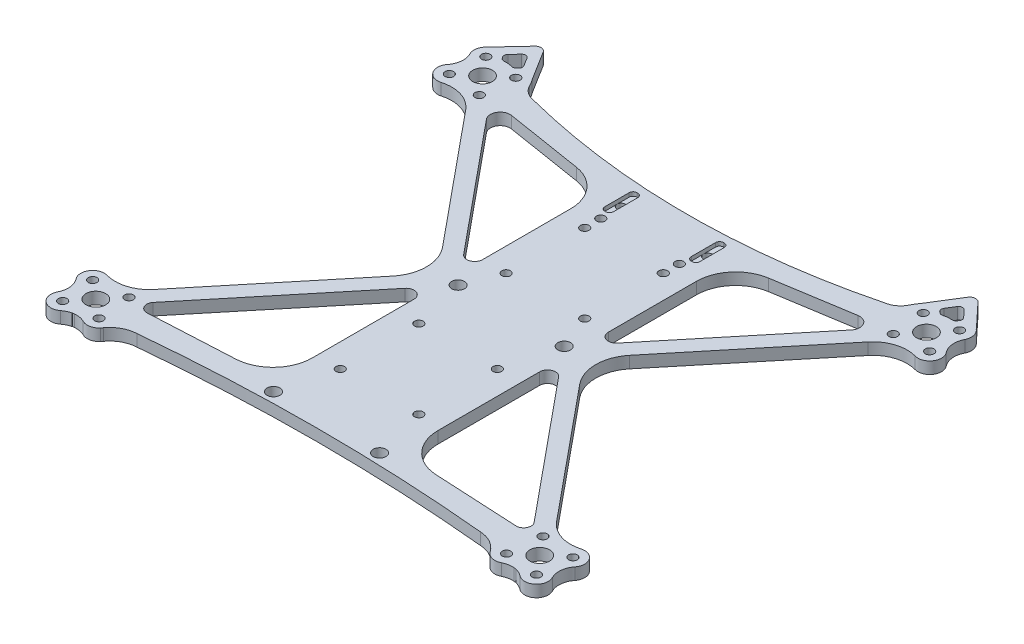
SolidWorks part; units mm, degrees
ref_plane "Front Plane" through (0, 0, 0) normal (0, 0, 1) x (1, 0, 0)
ref_plane "Top Plane" through (0, 0, 0) normal (0, 1, 0) x (1, 0, 0)
ref_plane "Right Plane" through (0, 0, 0) normal (1, 0, 0) x (0, 0, -1)
sketch "Sketch1" plane through (0, 0, 0) normal (0, 1, 0) x (1, 0, 0)
  line L0 (0, 42.225) -> (0, -42.225) construction
  line L1 (16, 42.225) -> (-16, 42.225)
  line L2 (16, 42.225) -> (16, -42.225)
  line L3 (16, -42.225) -> (-16, -42.225)
  line L4 (-16, 42.225) -> (-16, -42.225)
  line L5 (16, 42.225) -> (-16, -42.225) construction
  line L6 (16, -42.225) -> (-16, 42.225) construction
  line L17 (-16, 42.225) -> (16, 42.225)
  line L19 (-16, 42.225) -> (-16, 52.425)
  line L20 (-10, 36) -> (10, 36)
  line L21 (-10, 36) -> (-10, 16)
  line L22 (-10, 16) -> (10, 16)
  line L23 (10, 36) -> (10, 16)
  line L24 (-10, 36) -> (10, 16) construction
  line L25 (-10, 16) -> (10, 36) construction
  line L26 (-14.5, 10.775) -> (14.5, 10.775)
  line L27 (-14.5, 10.775) -> (-14.5, 41.225)
  line L28 (-14.5, 41.225) -> (14.5, 41.225)
  line L29 (14.5, 10.775) -> (14.5, 41.225)
  line L30 (-14.5, 10.775) -> (14.5, 41.225) construction
  line L31 (-14.5, 41.225) -> (14.5, 10.775) construction
  line L32 (-10, -6.225) -> (10, -6.225)
  line L33 (-10, -6.225) -> (-10, -26.225)
  line L34 (-10, -26.225) -> (10, -26.225)
  line L35 (10, -6.225) -> (10, -26.225)
  line L36 (-10, -6.225) -> (10, -26.225) construction
  line L37 (-10, -26.225) -> (10, -6.225) construction
  line L38 (-15.75, -36.225) -> (15.75, -36.225)
  line L39 (-15.75, -36.225) -> (-15.75, 3.775)
  line L40 (-15.75, 3.775) -> (15.75, 3.775)
  line L41 (15.75, -36.225) -> (15.75, 3.775)
  line L42 (-15.75, -36.225) -> (15.75, 3.775) construction
  line L43 (-15.75, 3.775) -> (15.75, -36.225) construction
  line L58 (-16, 52.425) -> (16, 52.425)
  line L63 (-12.1, 50.425) -> (-9.9, 50.425)
  line L64 (-12.1, 50.425) -> (-12.1, 42.225)
  line L65 (-12.1, 42.225) -> (-9.9, 42.225)
  line L66 (-9.9, 50.425) -> (-9.9, 42.225)
  line L67 (-12.1, 50.425) -> (-9.9, 42.225) construction
  line L68 (-12.1, 42.225) -> (-9.9, 50.425) construction
  line L78 (12.1, 50.425) -> (9.9, 50.425)
  line L79 (12.1, 50.425) -> (12.1, 42.225)
  line L80 (12.1, 42.225) -> (9.9, 42.225)
  line L81 (9.9, 50.425) -> (9.9, 42.225)
  line L82 (-14.5, 10.775) -> (-14.5, 3.775) construction
  line L83 (-14.5, 7.275) -> (16, 7.275) construction
  line L89 (-13.5, -37.225) -> (-16, -37.225) construction
  line L90 (16, 42.225) -> (16, 52.425)
  circle A3 centre (-10, 36) radius 1.1
  circle A4 centre (10, 36) radius 1.1
  circle A5 centre (10, 16) radius 1.1
  circle A6 centre (-10, 16) radius 1.1
  circle A7 centre (-10, -6.225) radius 1.1
  circle A8 centre (10, -6.225) radius 1.1
  circle A9 centre (10, -26.225) radius 1.1
  circle A10 centre (-10, -26.225) radius 1.1
  circle A37 centre (-13.5, 7.275) radius 2.5
  circle A38 centre (-13.5, 7.275) radius 1.625
  circle A39 centre (13.5, 7.275) radius 1.625
  circle A40 centre (-13.5, -39.725) radius 2.5
  circle A41 centre (-13.5, -39.725) radius 1.625
  circle A42 centre (13.5, -39.725) radius 1.625
  circle A43 centre (-11, 46.325) radius 1.1
  circle A44 centre (11, 46.325) radius 1.1
  point P0 (0, 0)
  point P8 (0, 0)
  point P16 (0, 26)
  point P26 (0, 26)
  point P31 (0, -16.225)
  point P36 (0, -16.225)
  point P61 (-11, 46.325)
  dimension "D3" = 22
  dimension "D4" = 2
  dimension "D17" = 2.2
  dimension "D22" = 5
  dimension "D23" = 3.25
  dimension "D8" = 32
  dimension "D10" = 20
  dimension "D11" = 29
  dimension "D12" = 30.45
  dimension "D13" = 40
  dimension "D14" = 31.5
  dimension "D15" = 1
  dimension "D16" = 7
  dimension "D18" = 2.2
  dimension "D20" = 8.2
  dimension "D24" = 1
extrude "Base shape" add sketch "Sketch1" along normal blind 2 contours L1 L90 L58 L19 L17 L64 L63 L66 L81 L78 L79 | A43 L64 L17 L66 | A43 L66 L63 L64 | L81 A44 L79 L78 | L79 A44 L81 L17 | L4 L3 L2 L1 | A3 | A4 | A6 | A5 | A39 | A38 | A7 | A8 | A9 | A10 | A41 | A42 region at (0, 0, -47.4493) region at (11, 0, -43.8523) region at (11, 0, -48.7977) region at (-11, 0, -43.8523) region at (-11, 0, -48.7977)
sketch "Sketch2" plane through (0, 2, 0) normal (0, -1, 0) x (1, 0, 0)
  line L0 (0, -52.425) -> (0, 42.225) construction
  line L1 (11.1, -42.225) -> (10.9, -42.225)
  line L2 (12.1, -43.225) -> (12.1, -49.425)
  line L3 (11.1, -50.425) -> (10.9, -50.425)
  line L4 (9.9, -43.225) -> (9.9, -49.425)
  line L5 (12.1, -42.225) -> (9.9, -50.425) construction
  line L6 (12.1, -50.425) -> (9.9, -42.225) construction
  line L12 (16, 42.225) -> (-16, 42.225) construction
  line L13 (-11.1, -42.225) -> (-10.9, -42.225)
  line L14 (-12.1, -43.225) -> (-12.1, -49.425)
  line L15 (-11.1, -50.425) -> (-10.9, -50.425)
  line L20 (-9.9, -43.225) -> (-9.9, -49.425)
  line L21 (-16, -52.425) -> (16, -52.425) construction
  arc A2 (12.1, -49.425) -> (11.1, -50.425) centre (11.1, -49.425) cw
  arc A3 (10.9, -50.425) -> (9.9, -49.425) centre (10.9, -49.425) cw
  arc A4 (10.9, -42.225) -> (9.9, -43.225) centre (10.9, -43.225) ccw
  arc A5 (11.1, -42.225) -> (12.1, -43.225) centre (11.1, -43.225) cw
  arc A6 (-10.9, -42.225) -> (-9.9, -43.225) centre (-10.9, -43.225) cw
  arc A7 (-11.1, -42.225) -> (-12.1, -43.225) centre (-11.1, -43.225) ccw
  arc A8 (-12.1, -49.425) -> (-11.1, -50.425) centre (-11.1, -49.425) ccw
  arc A9 (-10.9, -50.425) -> (-9.9, -49.425) centre (-10.9, -49.425) ccw
  point P0 (11, -46.325)
  dimension "D3" = 1
  dimension "D1" = 8.2
  dimension "D2" = 2.2
extrude "Cut-Extrude2" cut sketch "Sketch2" along normal blind 1
sketch "Sketch3" plane through (0, 2, 0) normal (0, 1, 0) x (1, 0, 0)
  line L0 (-11.1, 50.425) -> (-10.9, 50.425) construction
  line L1 (-9.9, 49.425) -> (-9.9, 43.225) construction
  line L2 (-10.9, 42.225) -> (-11.1, 42.225) construction
  line L3 (-12.1, 43.225) -> (-12.1, 49.425) construction
  line L4 (-11.1, 50.425) -> (-10.9, 50.425)
  line L5 (-9.9, 49.425) -> (-9.9, 43.225)
  line L6 (-10.9, 42.225) -> (-11.1, 42.225)
  line L7 (-12.1, 43.225) -> (-12.1, 49.425)
  line L8 (-16, 52.425) -> (-16, -42.225)
  line L9 (-16, 52.425) -> (-16, -42.225)
  line L10 (-16, -42.225) -> (16, -42.225)
  line L11 (16, -42.225) -> (16, 52.425)
  line L12 (10.9, 50.425) -> (11.1, 50.425) construction
  line L13 (12.1, 49.425) -> (12.1, 43.225) construction
  line L14 (11.1, 42.225) -> (10.9, 42.225) construction
  line L15 (9.9, 43.225) -> (9.9, 49.425) construction
  line L18 (-16, -42.225) -> (16, -42.225)
  line L24 (10.9, 50.425) -> (11.1, 50.425)
  line L25 (12.1, 49.425) -> (12.1, 43.225)
  line L30 (11.1, 42.225) -> (10.9, 42.225)
  line L31 (9.9, 43.225) -> (9.9, 49.425)
  line L36 (16, -42.225) -> (16, 52.425)
  line L37 (16, 52.425) -> (-16, 52.425)
  line L38 (16, 52.425) -> (-16, 52.425)
  circle A0 centre (13.5, -39.725) radius 1.625 construction
  circle A1 centre (-13.5, -39.725) radius 1.625 construction
  circle A2 centre (-13.5, 7.275) radius 1.625 construction
  circle A3 centre (-10, -6.225) radius 1.1 construction
  circle A4 centre (-10, -26.225) radius 1.1 construction
  circle A5 centre (10, -26.225) radius 1.1 construction
  circle A6 centre (10, -6.225) radius 1.1 construction
  circle A7 centre (13.5, 7.275) radius 1.625 construction
  arc A13 (-11.1, 50.425) -> (-12.1, 49.425) centre (-11.1, 49.425) ccw construction
  arc A14 (-9.9, 49.425) -> (-10.9, 50.425) centre (-10.9, 49.425) ccw construction
  circle A24 centre (-10, 16) radius 1.1 construction
  circle A25 centre (-10, 36) radius 1.1 construction
  circle A26 centre (10, 36) radius 1.1 construction
  circle A27 centre (10, 16) radius 1.1 construction
  circle A28 centre (10, 16) radius 1.1
  circle A29 centre (10, 36) radius 1.1
  circle A30 centre (-10, 36) radius 1.1
  circle A31 centre (-10, 16) radius 1.1
  circle A32 centre (13.5, 7.275) radius 1.625
  circle A33 centre (10, -6.225) radius 1.1
  circle A34 centre (10, -26.225) radius 1.1
  circle A35 centre (-10, -26.225) radius 1.1
  circle A36 centre (-10, -6.225) radius 1.1
  circle A37 centre (13.5, -39.725) radius 1.625
  circle A38 centre (-13.5, -39.725) radius 1.625
  circle A39 centre (-13.5, 7.275) radius 1.625
  arc A40 (-10.9, 42.225) -> (-9.9, 43.225) centre (-10.9, 43.225) ccw construction
  arc A41 (-12.1, 43.225) -> (-11.1, 42.225) centre (-11.1, 43.225) ccw construction
  arc A42 (-11.1, 50.425) -> (-12.1, 49.425) centre (-11.1, 49.425) ccw
  arc A43 (-9.9, 49.425) -> (-10.9, 50.425) centre (-10.9, 49.425) ccw
  arc A44 (-10.9, 42.225) -> (-9.9, 43.225) centre (-10.9, 43.225) ccw
  arc A45 (-12.1, 43.225) -> (-11.1, 42.225) centre (-11.1, 43.225) ccw
  arc A46 (10.9, 50.425) -> (9.9, 49.425) centre (10.9, 49.425) ccw construction
  arc A47 (12.1, 49.425) -> (11.1, 50.425) centre (11.1, 49.425) ccw construction
  arc A48 (11.1, 42.225) -> (12.1, 43.225) centre (11.1, 43.225) ccw construction
  arc A49 (9.9, 43.225) -> (10.9, 42.225) centre (10.9, 43.225) ccw construction
  arc A50 (10.9, 50.425) -> (9.9, 49.425) centre (10.9, 49.425) ccw
  arc A51 (12.1, 49.425) -> (11.1, 50.425) centre (11.1, 49.425) ccw
  arc A52 (11.1, 42.225) -> (12.1, 43.225) centre (11.1, 43.225) ccw
  arc A53 (9.9, 43.225) -> (10.9, 42.225) centre (10.9, 43.225) ccw
  dimension "D1" = 0
extrude "Thicker base" add sketch "Sketch3" along normal blind 1
sketch "Sketch8" plane through (0, 1, 0) normal (0, 1, 0) x (1, 0, 0)
  line L0 (9.9, 46.325) -> (9.9, 43.225) construction
  line L1 (10.9, 42.225) -> (11.1, 42.225) construction
  line L2 (12.1, 43.225) -> (12.1, 46.325) construction
  line L3 (12.1, 46.325) -> (12.1, 49.425) construction
  line L4 (11.1, 50.425) -> (10.9, 50.425) construction
  line L5 (9.9, 49.425) -> (9.9, 46.325) construction
  line L6 (-12.1, 46.325) -> (-12.1, 43.225) construction
  line L7 (-11.1, 42.225) -> (-10.9, 42.225) construction
  line L8 (-9.9, 43.225) -> (-9.9, 46.325) construction
  line L9 (-9.9, 46.325) -> (-9.9, 49.425) construction
  line L10 (-10.9, 50.425) -> (-11.1, 50.425) construction
  line L11 (-12.1, 49.425) -> (-12.1, 46.325) construction
  line L12 (9.9, 46.325) -> (9.9, 43.225)
  line L13 (10.9, 42.225) -> (11.1, 42.225)
  line L14 (12.1, 43.225) -> (12.1, 46.325)
  line L15 (12.1, 46.325) -> (12.1, 49.425)
  line L16 (11.1, 50.425) -> (10.9, 50.425)
  line L17 (9.9, 49.425) -> (9.9, 46.325)
  line L18 (-12.1, 46.325) -> (-12.1, 43.225)
  line L19 (-11.1, 42.225) -> (-10.9, 42.225)
  line L20 (-9.9, 43.225) -> (-9.9, 46.325)
  line L21 (-9.9, 46.325) -> (-9.9, 49.425)
  line L22 (-10.9, 50.425) -> (-11.1, 50.425)
  line L23 (-12.1, 49.425) -> (-12.1, 46.325)
  arc A0 (9.9, 46.325) -> (12.1, 46.325) centre (11, 46.325) ccw construction
  arc A1 (9.9, 43.225) -> (10.9, 42.225) centre (10.9, 43.225) ccw construction
  arc A2 (11.1, 42.225) -> (12.1, 43.225) centre (11.1, 43.225) ccw construction
  arc A3 (12.1, 46.325) -> (9.9, 46.325) centre (11, 46.325) ccw construction
  arc A4 (12.1, 49.425) -> (11.1, 50.425) centre (11.1, 49.425) ccw construction
  arc A5 (10.9, 50.425) -> (9.9, 49.425) centre (10.9, 49.425) ccw construction
  arc A6 (-12.1, 43.225) -> (-11.1, 42.225) centre (-11.1, 43.225) ccw construction
  arc A7 (-10.9, 42.225) -> (-9.9, 43.225) centre (-10.9, 43.225) ccw construction
  arc A8 (-12.1, 46.325) -> (-9.9, 46.325) centre (-11, 46.325) ccw construction
  arc A9 (-9.9, 49.425) -> (-10.9, 50.425) centre (-10.9, 49.425) ccw construction
  arc A10 (-11.1, 50.425) -> (-12.1, 49.425) centre (-11.1, 49.425) ccw construction
  arc A11 (-9.9, 46.325) -> (-12.1, 46.325) centre (-11, 46.325) ccw construction
  arc A12 (9.9, 46.325) -> (12.1, 46.325) centre (11, 46.325) ccw
  arc A13 (9.9, 43.225) -> (10.9, 42.225) centre (10.9, 43.225) ccw
  arc A14 (11.1, 42.225) -> (12.1, 43.225) centre (11.1, 43.225) ccw
  arc A15 (12.1, 46.325) -> (9.9, 46.325) centre (11, 46.325) ccw
  arc A16 (12.1, 49.425) -> (11.1, 50.425) centre (11.1, 49.425) ccw
  arc A17 (10.9, 50.425) -> (9.9, 49.425) centre (10.9, 49.425) ccw
  arc A18 (-12.1, 43.225) -> (-11.1, 42.225) centre (-11.1, 43.225) ccw
  arc A19 (-10.9, 42.225) -> (-9.9, 43.225) centre (-10.9, 43.225) ccw
  arc A20 (-12.1, 46.325) -> (-9.9, 46.325) centre (-11, 46.325) ccw
  arc A21 (-9.9, 49.425) -> (-10.9, 50.425) centre (-10.9, 49.425) ccw
  arc A22 (-11.1, 50.425) -> (-12.1, 49.425) centre (-11.1, 49.425) ccw
  arc A23 (-9.9, 46.325) -> (-12.1, 46.325) centre (-11, 46.325) ccw
  line M1 (-9.9, 46.325) -> (-9.9, 49.425)
  arc M2 (-9.9, 49.425) -> (-10.9, 50.425) centre (-10.9, 49.425) ccw
  line M3 (-10.9, 50.425) -> (-11.1, 50.425)
  arc M4 (-11.1, 50.425) -> (-12.1, 49.425) centre (-11.1, 49.425) ccw
  line M5 (-12.1, 49.425) -> (-12.1, 46.325)
  arc M6 (-12.1, 46.325) -> (-9.9, 46.325) centre (-11, 46.325) cw
extrude "Thicker camera mount pocket" add sketch "Sketch8" along normal offset from surface (1 mm away) 1 contours A20 L18 A18 L19 A19 L20 | M6 M1 M2 M3 M4 M5 | L16 A17 L17 A15 L15 A16 | L13 A14 L14 A12 L12 A13 region at (11, 1, -43.9424) region at (11, 1, -48.7076) region at (-11, 1, -43.9424) region at (-11, 1, -48.7076) up to face at (-13.5, 3, 41.35)
sketch "Sketch4" plane through (0, 0, 0) normal (0, -1, 0) x (1, 0, 0)
  line L0 (0, 13.9568) -> (0, -8.6953) construction
  line L1 (-13.1, -38.5) -> (-6.9, -38.5)
  line L2 (-14.1, -39.5) -> (-14.1, -40.7)
  line L3 (-13.1, -41.7) -> (-6.9, -41.7)
  line L4 (-5.9, -39.5) -> (-5.9, -40.7)
  line L5 (-10, -38.5) -> (-10, -41.7) construction
  line L7 (13.1, -38.5) -> (6.9, -38.5)
  line L8 (14.1, -39.5) -> (14.1, -40.7)
  line L9 (13.1, -41.7) -> (6.9, -41.7)
  line L10 (5.9, -39.5) -> (5.9, -40.7)
  line L12 (-14.1, -40.1) -> (-5.9, -40.1) construction
  circle A0 centre (-10, -36) radius 2
  arc A9 (14.1, -40.7) -> (13.1, -41.7) centre (13.1, -40.7) cw
  arc A10 (13.1, -38.5) -> (14.1, -39.5) centre (13.1, -39.5) cw
  arc A11 (6.9, -41.7) -> (5.9, -40.7) centre (6.9, -40.7) cw
  arc A12 (6.9, -38.5) -> (5.9, -39.5) centre (6.9, -39.5) ccw
  arc A13 (-6.9, -41.7) -> (-5.9, -40.7) centre (-6.9, -40.7) ccw
  arc A14 (-6.9, -38.5) -> (-5.9, -39.5) centre (-6.9, -39.5) cw
  arc A15 (-14.1, -40.7) -> (-13.1, -41.7) centre (-13.1, -40.7) ccw
  arc A16 (-13.1, -38.5) -> (-14.1, -39.5) centre (-13.1, -39.5) ccw
  point P9 (-10, -38)
  point P19 (14.1, -41.7)
  point P24 (14.1, -38.5)
  point P27 (5.9, -41.7)
  point P30 (5.9, -38.5)
  point P33 (-5.9, -41.7)
  point P36 (-5.9, -38.5)
  point P39 (-14.1, -41.7)
  point P42 (-14.1, -38.5)
  dimension "D5" = 4
  dimension "D6" = 1
  dimension "D1" = 8.2
  dimension "D2" = 3.2
  dimension "D3" = 10
  dimension "D4" = 0.5
extrude "Battery holder pockets" cut sketch "Sketch4" against normal blind 1 contours L4 L1 L2 L3 | L7 L10 L9 L8 region at (-10, 0, -40.1) region at (10, 0, -40.1)
sketch "Sketch5" plane through (0, 1, 0) normal (0, -1, 0) x (1, 0, 0)
  line L0 (-10, -38.5) -> (-10, -41.7) construction
  line L2 (-13.1, -41.7) -> (-6.9, -41.7) construction
  line L3 (0, 5.9884) -> (0, -5.6723) construction
  line L4 (-13.1, -38.5) -> (-6.9, -38.5) construction
  circle A0 centre (-10, -40.1) radius 1.1
  circle A1 centre (10, -40.1) radius 1.1
  dimension "D1" = 2.2
extrude "Battery holder holes" cut sketch "Sketch5" against normal up to next
sketch "Sketch6" [suppressed] plane through (0, 0, 0) normal (0, -1, 0) x (1, 0, 0)
  line L0 (0, -5.1) -> (0, 9.653) construction
  line L1 (16, 42.225) -> (16, -52.425) construction
  line L8 (-13.5, -7.275) -> (13.5, -7.275) construction
  line L10 (-16, -25.775) -> (16, -25.775) construction
  line L13 (17.5, -34.275) -> (19, -34.275)
  line L14 (16, -37.275) -> (19, -37.275)
  line L15 (16, -37.275) -> (16, -14.275)
  line L16 (16, -14.275) -> (19, -14.275)
  line L17 (19, -37.275) -> (19, -14.275)
  line L18 (16, -37.275) -> (19, -14.275) construction
  line L19 (16, -14.275) -> (19, -37.275) construction
  line L20 (16, -35.775) -> (17.5, -35.775)
  line L21 (16, -35.775) -> (16, -15.775)
  line L22 (16, -15.775) -> (17.5, -15.775)
  line L23 (17.5, -35.775) -> (17.5, -15.775)
  line L24 (16, -35.775) -> (17.5, -15.775) construction
  line L25 (16, -15.775) -> (17.5, -35.775) construction
  line L26 (17.5, -17.275) -> (19, -17.275)
  line L27 (-17.5, -34.275) -> (-19, -34.275)
  line L28 (-17.5, -17.275) -> (-19, -17.275)
  line L29 (-16, -35.775) -> (-16, -15.775)
  line L30 (-16, -35.775) -> (-17.5, -35.775)
  line L31 (-17.5, -35.775) -> (-17.5, -15.775)
  line L32 (-16, -15.775) -> (-17.5, -15.775)
  line L33 (-16, -37.275) -> (-16, -14.275)
  line L34 (-16, -37.275) -> (-19, -37.275)
  line L35 (-19, -37.275) -> (-19, -14.275)
  line L36 (-16, -14.275) -> (-19, -14.275)
  line L37 (16, 22.725) -> (19, 22.725)
  line L38 (16, 22.725) -> (16, -0.275)
  line L39 (16, -0.275) -> (19, -0.275)
  line L40 (19, 22.725) -> (19, -0.275)
  line L41 (16, 21.225) -> (17.5, 21.225)
  line L42 (16, 21.225) -> (16, 1.225)
  line L43 (16, 1.225) -> (17.5, 1.225)
  line L44 (17.5, 21.225) -> (17.5, 1.225)
  line L45 (17.5, 2.725) -> (19, 2.725)
  line L46 (17.5, 19.725) -> (19, 19.725)
  line L47 (-17.5, 19.725) -> (-19, 19.725)
  line L48 (-17.5, 2.725) -> (-19, 2.725)
  line L49 (-16, 21.225) -> (-16, 1.225)
  line L50 (-16, 21.225) -> (-17.5, 21.225)
  line L51 (-17.5, 21.225) -> (-17.5, 1.225)
  line L52 (-16, 1.225) -> (-17.5, 1.225)
  line L53 (-16, 22.725) -> (-16, -0.275)
  line L54 (-16, 22.725) -> (-19, 22.725)
  line L55 (-19, 22.725) -> (-19, -0.275)
  line L56 (-16, -0.275) -> (-19, -0.275)
  point P19 (17.5, -25.775)
  point P25 (16.75, -25.775)
  dimension "D1" = 14
  dimension "D4" = 23
  dimension "D5" = 3
  dimension "D6" = 1.5
  dimension "D7" = 20
  dimension "D8" = 1.5
extrude "Strap holders" [suppressed] add sketch "Sketch6" against normal up to surface (2 mm away) up to face at (-11, 2, -43.6726)
fillet "Strap holder fillets" [suppressed] radius 0.75
fillet "Edge fillets" [suppressed] radius 2.5
sketch "Sketch7" plane through (0, 3, 0) normal (0, 1, 0) x (1, 0, 0)
  line L0 (-56.5, 56.5) -> (-16, 50.0116) construction
  line L1 (56.5, -56.5) -> (-56.5, -56.5)
  line L2 (56.5, -56.5) -> (56.5, 56.5)
  line L3 (56.5, 56.5) -> (-56.5, 56.5)
  line L4 (-56.5, -56.5) -> (-56.5, 56.5)
  line L5 (56.5, -56.5) -> (-56.5, 56.5) construction
  line L6 (56.5, 56.5) -> (-56.5, -56.5) construction
  line L7 (-16, 46.9733) -> (-48.5961, 52.1955)
  line L8 (-16, 4.1271) -> (-52.4693, 48.4531)
  line L9 (-47.647, 58.1199) -> (-12.1, 52.425)
  line L10 (-56.0254, 59.4622) -> (-15.5254, 52.9738) construction
  line L11 (-13.5, 7.275) -> (13.5, 7.275) construction
  line L12 (-63.45, 50.7819) -> (-49.55, 62.2181) construction
  line L13 (-56.5, 56.5) -> (-16, 7.275) construction
  line L14 (-16, 10.4229) -> (-52.4693, -33.9031)
  line L15 (-49.3804, 50.9945) -> (-16, 10.4229)
  line L16 (-16, 4.1271) -> (-16.003, 4.1308)
  line L17 (-56.5, 56.5) -> (-60.3121, 61.1333) construction
  line L18 (-56.5, 65.5) -> (-56.5, 47.5) construction
  line L19 (-60.3121, 61.1333) -> (-51.8667, 60.3121) construction
  line L20 (-56.0894, 60.7227) -> (-55.3151, 68.6852) construction
  line L21 (-56.4116, 69.7087) -> (-62.3842, 63.31)
  line L22 (-54.0419, 69.4782) -> (-49.414, 62.0488)
  line L23 (-55.4603, 67.1922) -> (-58.7341, 63.6848)
  line L24 (-55.4603, 67.1922) -> (-52.9235, 63.1198)
  line L25 (-36.25, 53.2558) -> (-36.7246, 50.2936) construction
  line L26 (-49.3804, -36.4445) -> (-16, 4.1271)
  line L27 (-56.5, -41.95) -> (-13.5, -39.725) construction
  line L28 (-47.871, -44.5075) -> (-3.7595, -42.225)
  line L29 (-48.1811, -38.5155) -> (-16, -36.8503)
  line L30 (-56.345, -44.946) -> (-14.5762, -42.7847) construction
  line L31 (-56.5, -41.95) -> (-14.7312, -39.7887) construction
  line L32 (-16, -42.225) -> (16, -42.225) construction
  line L33 (-56.655, -38.954) -> (-14.8862, -36.7927) construction
  line L34 (-35, -40.8375) -> (-35.155, -37.8415) construction
  line L35 (-12.1, 49.425) -> (-12.1, 52.425) construction
  line L37 (16, 52.425) -> (-16, 52.425) construction
  line L38 (-16, 52.425) -> (-16, -42.225) construction
  line L39 (-54.9556, 57.7707) -> (-12.9111, 6.6685) construction
  line L40 (-56.5, 56.5) -> (-14.4556, 5.3978) construction
  circle A0 centre (-56.5, 56.5) radius 38.1
  circle A1 centre (-56.5, 56.5) radius 9
  circle A2 centre (-56.5, 56.5) radius 6
  circle A3 centre (-51.8667, 60.3121) radius 1.1
  circle A4 centre (-61.1333, 52.6879) radius 1.1
  circle A5 centre (-60.3121, 61.1333) radius 1.1
  circle A6 centre (-52.6879, 51.8667) radius 1.1
  circle A7 centre (-60.3121, 61.1333) radius 3
  circle A8 centre (-51.8667, 60.3121) radius 3
  circle A9 centre (-61.1333, 52.6879) radius 3
  circle A10 centre (-52.6879, 51.8667) radius 3
  circle A12 centre (-56.5, 56.5) radius 2.5
  circle A13 centre (-55.3151, 68.6852) radius 1.5
  circle A14 centre (-67.313, 57.5515) radius 4.864
  circle A16 centre (-43.9819, 62.4587) radius 4.864
  circle A18 centre (-44.5093, 49.0089) radius 2.5
  circle A20 centre (-56.5, -41.95) radius 6
  circle A21 centre (-52.6879, -37.3167) radius 1.1
  circle A22 centre (-61.1333, -38.1379) radius 1.1
  circle A23 centre (-60.3121, -46.5833) radius 1.1
  circle A24 centre (-51.8667, -45.7621) radius 1.1
  circle A25 centre (-51.8667, -45.7621) radius 3
  circle A26 centre (-52.6879, -37.3167) radius 3
  circle A27 centre (-56.5, -41.95) radius 2.5
  circle A28 centre (-60.3121, -46.5833) radius 3
  circle A29 centre (-67.313, -43.0015) radius 4.864
  circle A30 centre (-61.1333, -38.1379) radius 3
  circle A34 centre (-56.5, -41.95) radius 9
  circle A35 centre (-55.4485, -52.763) radius 4.864
  circle A36 centre (-57.9703, 41.3803) radius 8.7417
  circle A37 centre (-57.9703, -26.8303) radius 8.7417
  circle A38 centre (-43.36, -51.5674) radius 7.2836
  circle A39 centre (-47.0369, -36.5665) radius 1.8873
  point P0 (0, 0)
  point P36 (-52.6879, 51.8667)
  point P54 (-55.4603, 67.1922)
  line M26 (-16, -42.225) -> (16, -42.225)
  line M134 (16, 52.425) -> (-16, 52.425)
  line M135 (-16, 52.425) -> (-16, -42.225)
  dimension "D3" = 76.2
  dimension "D4" = 12
  dimension "D5" = 3
  dimension "D10" = 2.2
  dimension "D11" = 5
  dimension "D12" = 3
  dimension "D16" = 5
  dimension "D1" = 113
  dimension "D13" = 8
  dimension "D7" = 3
  dimension "D9" = 2
extrude "Arms" add sketch "Sketch7" against normal up to surface (3 mm away) contours A0 L7 L9 M135 M134 | A1 L7 A0 L9 L3 | A1 L3 L9 | A8 A2 L3 A1 | A16 A1 L9 | A10 A1 L3 A2 | A18 L7 A1 L15 | A2 A8 A3 | A2 A8 A3 | A8 A1 L24 | A13 L24 A1 L22 | A13 | A13 L21 A1 L23 | A7 L23 A1 | A2 A7 A5 | A2 A7 A5 | A12 L3 A2 A8 A7 A9 L4 | A12 L4 A2 A10 L3 | A2 A10 A6 | A10 A2 A6 | A36 A1 A10 | A36 L8 A1 | A36 A10 A2 L4 | A36 L4 A2 A9 | A2 A9 A4 | A2 A9 A4 | A14 A9 A2 | A14 A2 A7 | A1 L8 A0 L15 | A0 L8 L14 L15 | L14 L8 M135 | L14 A34 L26 L8 | L29 A34 L28 M26 M135 | A39 A34 L29 | A39 L26 A34 | L14 A37 A34 | A34 A37 A26 | A34 A26 A20 A25 | A26 A20 A21 | A26 A37 L4 A20 | A26 A20 A21 | L4 A27 A20 A25 A26 | A25 A20 A24 | A38 L28 A34 | A25 A20 A24 | A20 A30 A28 L4 A27 | L4 A37 A30 A20 | A30 A20 A22 | A30 A20 A22 | A20 A30 A29 | A20 A29 A28 | A28 A20 A23 | A28 A20 A23 | A35 L4 A20 A28 | A35 A25 A20 region at (-47.184, 3, 45.066) region at (-31.4436, 3, 40.7044) region at (-32.8289, 3, -52.5874) region at (-44.211, 3, -57.0386) region at (-17.2942, 3, -50.2467) region at (-49.0289, 3, 41.2235) region at (-49.1542, 3, -54.332) region at (-48.8324, 3, -58.0351) region at (-47.1282, 3, -58.5028) region at (-24.8075, 3, -17.9625) region at (-41.5668, 3, -38.3497) region at (-61.0916, 3, 47.5307) region at (-57.4052, 3, 48.163) region at (-50.9193, 3, 46.5416) region at (-54.4445, 3, 47.8724) region at (-50.6896, 3, -55.3917) region at (-52.25, 3, -56.6697) region at (-47.4889, 3, -50.715) region at (-16.8633, 3, -7.275) region at (-34.0657, 3, 14.6748) region at (-52.2257, 3, -48.0457) region at (-62.4224, 3, 44.0055) region at (-57.252, 3, 47.2609) region at (-59.3254, 3, 45.3841) region at (-53.0659, 3, 44.7754) region at (-55.123, 3, 47.6519) region at (-48.0098, 3, 38.2823) region at (-53.0659, 3, -59.3254) region at (-50.9193, 3, -61.0916) region at (-51.9084, 3, -50.9193) region at (-53.6746, 3, -53.0659) region at (-52.9788, 3, -65.9755) region at (-55.6399, 3, 35.5458) region at (-58.0636, 3, 35.804) region at (-52.2257, 3, 33.4957) region at (-52.5163, 3, 34.2128) region at (-62.0807, 3, 37.3584) region at (-58.0636, 3, -50.354) region at (-55.6399, 3, -50.0958) region at (-52.5163, 3, -48.7628) region at (-62.0807, 3, -51.9084) region at (-49.026, 3, 36.4293) region at (-55.3151, 3, -68.6852) region at (-52.4447, 3, -63.9477) region at (-51.9084, 3, 36.3693) region at (-62.7075, 3, 41.0741) region at (-59.9341, 3, 39.1246) region at (-62.7075, 3, -55.6241) region at (-59.9341, 3, -53.6746) region at (-59.3254, 3, -59.9341) region at (-61.0916, 3, -62.0807) region at (-58.1296, 3, -66.4764) region at (-53.6746, 3, 38.5159) region at (-62.4224, 3, -58.5555) region at (-59.0444, 3, -64.5895) up to face at (-13.5, 0, 41.35)
fillet "Motor protector fillets" radius 1 5 edges at (-52.9235, 1.5, -63.1198) (-54.2913, 1.5, -62.0787) (-57.5925, 1.5, -62.3997) (-58.7341, 1.5, -63.6848) (-55.4603, 1.5, -67.1922)
mirror "Arms mirror" about plane through (0, 0, 0) normal (1, 0, 0) of "Arms", "Motor protector fillets"
fillet "Arm fillets outer" radius 10 6 edges at (16, 1.5, 36.8503) (-16, 1.5, 36.8503) (-18.5899, 1.5, -7.275) (18.5899, 1.5, -7.275) (16, 1.5, -46.9733) (-16, 1.5, -46.9733)
fillet "Arm fillets inner" radius 2 4 edges at (16, 1.5, -10.4229) (16, 1.5, -4.1271) (-16, 1.5, -4.1271) (-16, 1.5, -10.4229)
sketch "Sketch9" plane through (0, 0, 0) normal (0, -1, 0) x (1, 0, 0)
  line L0 (0, 56.7966) -> (0, -145.2298) construction
  line L5 (12.1, -52.425) -> (44.7513, -57.656)
  line L10 (12.1, -52.425) -> (44.7513, -57.656)
  line L21 (-12.1, -52.425) -> (12.1, -52.425)
  line L25 (49.414, -62.0488) -> (54.0419, -69.4782)
  line L26 (49.414, -62.0488) -> (54.0419, -69.4782)
  line L28 (56.4116, -69.7087) -> (62.3842, -63.31)
  line L30 (56.4116, -69.7087) -> (62.3842, -63.31)
  line L31 (3.7595, 42.225) -> (-3.7595, 42.225)
  line L33 (56.5, 48.014) -> (56.5, 47.95)
  line L35 (56.5, 48.014) -> (56.5, 47.95)
  line L37 (43.7364, 44.2936) -> (3.7595, 42.225)
  line L39 (43.7364, 44.2936) -> (3.7595, 42.225)
  line L41 (-12.1, -52.425) -> (12.1, -52.425)
  line L51 (3.7595, 42.225) -> (-3.7595, 42.225)
  line L61 (51.2197, -46.9343) -> (23.8173, -13.6285)
  line L63 (51.2197, -46.9343) -> (23.8173, -13.6285)
  line L65 (23.8173, -0.9215) -> (51.2197, 32.3843)
  line L67 (23.8173, -0.9215) -> (51.2197, 32.3843)
  line L69 (-3.7595, 42.225) -> (-43.7364, 44.2936)
  line L71 (-3.7595, 42.225) -> (-43.7364, 44.2936)
  line L73 (-56.5, 47.95) -> (-56.5, 48.014)
  line L75 (-56.5, 47.95) -> (-56.5, 48.014)
  line L77 (-51.2197, 32.3843) -> (-23.8173, -0.9215)
  line L79 (-51.2197, 32.3843) -> (-23.8173, -0.9215)
  line L81 (-23.8173, -13.6285) -> (-51.2197, -46.9343)
  line L82 (-23.8173, -13.6285) -> (-51.2197, -46.9343)
  line L83 (-62.3842, -63.31) -> (-56.4116, -69.7087)
  line L84 (-62.3842, -63.31) -> (-56.4116, -69.7087)
  line L85 (-54.0419, -69.4782) -> (-49.414, -62.0488)
  line L86 (-54.0419, -69.4782) -> (-49.414, -62.0488)
  line L87 (-44.7513, -57.656) -> (-12.1, -52.425)
  line L88 (-44.7513, -57.656) -> (-12.1, -52.425)
  circle A0 centre (0, -232.4697) radius 180.4509
  circle A1 centre (0, 502.2082) radius 459.9986
  arc A38 (48.3737, -60.3682) -> (44.7513, -57.656) centre (43.9819, -62.4587) ccw
  arc A39 (48.3737, -60.3682) -> (44.7513, -57.656) centre (43.9819, -62.4587) ccw
  arc A40 (48.3737, -60.3682) -> (49.414, -62.0488) centre (56.5, -56.5) ccw
  arc A41 (48.3737, -60.3682) -> (49.414, -62.0488) centre (56.5, -56.5) ccw
  arc A42 (54.0419, -69.4782) -> (56.4116, -69.7087) centre (55.3151, -68.6852) ccw
  arc A43 (54.0419, -69.4782) -> (56.4116, -69.7087) centre (55.3151, -68.6852) ccw
  arc A44 (62.2181, -63.45) -> (62.3842, -63.31) centre (56.5, -56.5) ccw
  arc A45 (62.2181, -63.45) -> (62.3842, -63.31) centre (56.5, -56.5) ccw
  arc A46 (62.2181, -63.45) -> (62.9828, -59.7669) centre (60.3121, -61.1333) ccw
  arc A47 (62.2181, -63.45) -> (62.9828, -59.7669) centre (60.3121, -61.1333) ccw
  arc A48 (63.4908, -54.5433) -> (62.9828, -59.7669) centre (67.313, -57.5515) ccw
  arc A50 (63.4908, -54.5433) -> (62.9828, -59.7669) centre (67.313, -57.5515) ccw
  arc A52 (63.4908, -54.5433) -> (60.3252, -49.7988) centre (61.1333, -52.6879) ccw
  arc A54 (63.4908, -54.5433) -> (60.3252, -49.7988) centre (61.1333, -52.6879) ccw
  arc A56 (51.2197, -46.9343) -> (60.3252, -49.7988) centre (57.9703, -41.3803) ccw
  arc A58 (51.2197, -46.9343) -> (60.3252, -49.7988) centre (57.9703, -41.3803) ccw
  arc A60 (56.5, 47.95) -> (55.9193, 47.9218) centre (56.5, 41.95) ccw
  arc A62 (56.5, 47.95) -> (55.9193, 47.9218) centre (56.5, 41.95) ccw
  arc A64 (60.3252, 35.2488) -> (63.4908, 39.9933) centre (61.1333, 38.1379) ccw
  arc A66 (60.3252, 35.2488) -> (63.4908, 39.9933) centre (61.1333, 38.1379) ccw
  arc A68 (62.9828, 45.2169) -> (63.4908, 39.9933) centre (67.313, 43.0015) ccw
  arc A70 (62.9828, 45.2169) -> (63.4908, 39.9933) centre (67.313, 43.0015) ccw
  arc A72 (62.9828, 45.2169) -> (58.4567, 48.9408) centre (60.3121, 46.5833) ccw
  arc A74 (62.9828, 45.2169) -> (58.4567, 48.9408) centre (60.3121, 46.5833) ccw
  arc A76 (56.5, 48.014) -> (58.4567, 48.9408) centre (55.4485, 52.763) ccw
  arc A78 (56.5, 48.014) -> (58.4567, 48.9408) centre (55.4485, 52.763) ccw
  arc A80 (53.2331, 48.4328) -> (55.9193, 47.9218) centre (55.4485, 52.763) ccw
  arc A82 (53.2331, 48.4328) -> (55.9193, 47.9218) centre (55.4485, 52.763) ccw
  arc A84 (53.2331, 48.4328) -> (49.55, 47.6681) centre (51.8667, 45.7621) ccw
  arc A86 (53.2331, 48.4328) -> (49.55, 47.6681) centre (51.8667, 45.7621) ccw
  arc A88 (49.55, 47.6681) -> (49.2375, 47.2656) centre (56.5, 41.95) ccw
  arc A90 (49.55, 47.6681) -> (49.2375, 47.2656) centre (56.5, 41.95) ccw
  arc A92 (43.7364, 44.2936) -> (49.2375, 47.2656) centre (43.36, 51.5674) ccw
  arc A94 (43.7364, 44.2936) -> (49.2375, 47.2656) centre (43.36, 51.5674) ccw
  arc A96 (60.3252, 35.2488) -> (51.2197, 32.3843) centre (57.9703, 26.8303) ccw
  arc A98 (60.3252, 35.2488) -> (51.2197, 32.3843) centre (57.9703, 26.8303) ccw
  arc A100 (-49.2375, 47.2656) -> (-43.7364, 44.2936) centre (-43.36, 51.5674) ccw
  arc A102 (-49.2375, 47.2656) -> (-43.7364, 44.2936) centre (-43.36, 51.5674) ccw
  arc A104 (-49.2375, 47.2656) -> (-49.55, 47.6681) centre (-56.5, 41.95) ccw
  arc A106 (-49.2375, 47.2656) -> (-49.55, 47.6681) centre (-56.5, 41.95) ccw
  arc A108 (-49.55, 47.6681) -> (-53.2331, 48.4328) centre (-51.8667, 45.7621) ccw
  arc A164 (-49.55, 47.6681) -> (-53.2331, 48.4328) centre (-51.8667, 45.7621) ccw
  arc A166 (-55.9193, 47.9218) -> (-53.2331, 48.4328) centre (-55.4485, 52.763) ccw
  arc A168 (-55.9193, 47.9218) -> (-53.2331, 48.4328) centre (-55.4485, 52.763) ccw
  arc A170 (-55.9193, 47.9218) -> (-56.5, 47.95) centre (-56.5, 41.95) ccw
  arc A172 (-55.9193, 47.9218) -> (-56.5, 47.95) centre (-56.5, 41.95) ccw
  arc A174 (-58.4567, 48.9408) -> (-56.5, 48.014) centre (-55.4485, 52.763) ccw
  arc A176 (-58.4567, 48.9408) -> (-56.5, 48.014) centre (-55.4485, 52.763) ccw
  arc A178 (-58.4567, 48.9408) -> (-62.9828, 45.2169) centre (-60.3121, 46.5833) ccw
  arc A180 (-58.4567, 48.9408) -> (-62.9828, 45.2169) centre (-60.3121, 46.5833) ccw
  arc A182 (-63.4908, 39.9933) -> (-62.9828, 45.2169) centre (-67.313, 43.0015) ccw
  arc A184 (-63.4908, 39.9933) -> (-62.9828, 45.2169) centre (-67.313, 43.0015) ccw
  arc A186 (-63.4908, 39.9933) -> (-60.3252, 35.2488) centre (-61.1333, 38.1379) ccw
  arc A188 (-63.4908, 39.9933) -> (-60.3252, 35.2488) centre (-61.1333, 38.1379) ccw
  arc A190 (-51.2197, 32.3843) -> (-60.3252, 35.2488) centre (-57.9703, 26.8303) ccw
  arc A192 (-51.2197, 32.3843) -> (-60.3252, 35.2488) centre (-57.9703, 26.8303) ccw
  arc A194 (-60.3252, -49.7988) -> (-51.2197, -46.9343) centre (-57.9703, -41.3803) ccw
  arc A195 (-60.3252, -49.7988) -> (-51.2197, -46.9343) centre (-57.9703, -41.3803) ccw
  arc A196 (-60.3252, -49.7988) -> (-63.4908, -54.5433) centre (-61.1333, -52.6879) ccw
  arc A197 (-60.3252, -49.7988) -> (-63.4908, -54.5433) centre (-61.1333, -52.6879) ccw
  arc A198 (-62.9828, -59.7669) -> (-63.4908, -54.5433) centre (-67.313, -57.5515) ccw
  arc A199 (-62.9828, -59.7669) -> (-63.4908, -54.5433) centre (-67.313, -57.5515) ccw
  arc A200 (-62.9828, -59.7669) -> (-62.2181, -63.45) centre (-60.3121, -61.1333) ccw
  arc A201 (-62.9828, -59.7669) -> (-62.2181, -63.45) centre (-60.3121, -61.1333) ccw
  arc A202 (-62.3842, -63.31) -> (-62.2181, -63.45) centre (-56.5, -56.5) ccw
  arc A203 (-62.3842, -63.31) -> (-62.2181, -63.45) centre (-56.5, -56.5) ccw
  arc A204 (-56.4116, -69.7087) -> (-54.0419, -69.4782) centre (-55.3151, -68.6852) ccw
  arc A205 (-56.4116, -69.7087) -> (-54.0419, -69.4782) centre (-55.3151, -68.6852) ccw
  arc A206 (-49.414, -62.0488) -> (-48.3737, -60.3682) centre (-56.5, -56.5) ccw
  arc A207 (-49.414, -62.0488) -> (-48.3737, -60.3682) centre (-56.5, -56.5) ccw
  arc A208 (-44.7513, -57.656) -> (-48.3737, -60.3682) centre (-43.9819, -62.4587) ccw
  arc A209 (-44.7513, -57.656) -> (-48.3737, -60.3682) centre (-43.9819, -62.4587) ccw
  arc A212 (23.8173, -0.9215) -> (23.8173, -13.6285) centre (31.5395, -7.275) ccw
  arc A213 (23.8173, -0.9215) -> (23.8173, -13.6285) centre (31.5395, -7.275) ccw
  arc A214 (-23.8173, -13.6285) -> (-23.8173, -0.9215) centre (-31.5395, -7.275) ccw
  arc A215 (-23.8173, -13.6285) -> (-23.8173, -0.9215) centre (-31.5395, -7.275) ccw
  dimension "D1" = 0
extrude "Front radius" cut sketch "Sketch9" against normal up to next contours A0 | L0 A0 L41 | A0 L0 L41 | L10 A0 | A1 | L39 A1 | L51 L0 A1 | L0 L51 A1 region at (1.4098, 0, 42.2189) region at (-1.4098, 0, 42.2189) region at (23.7569, 0, 43.0853) region at (-23.7569, 0, 43.0853) region at (4.5382, 0, -52.2625) region at (-4.5382, 0, -52.2625) region at (28.4737, 0, -54.7407) region at (-28.4737, 0, -54.7407)
